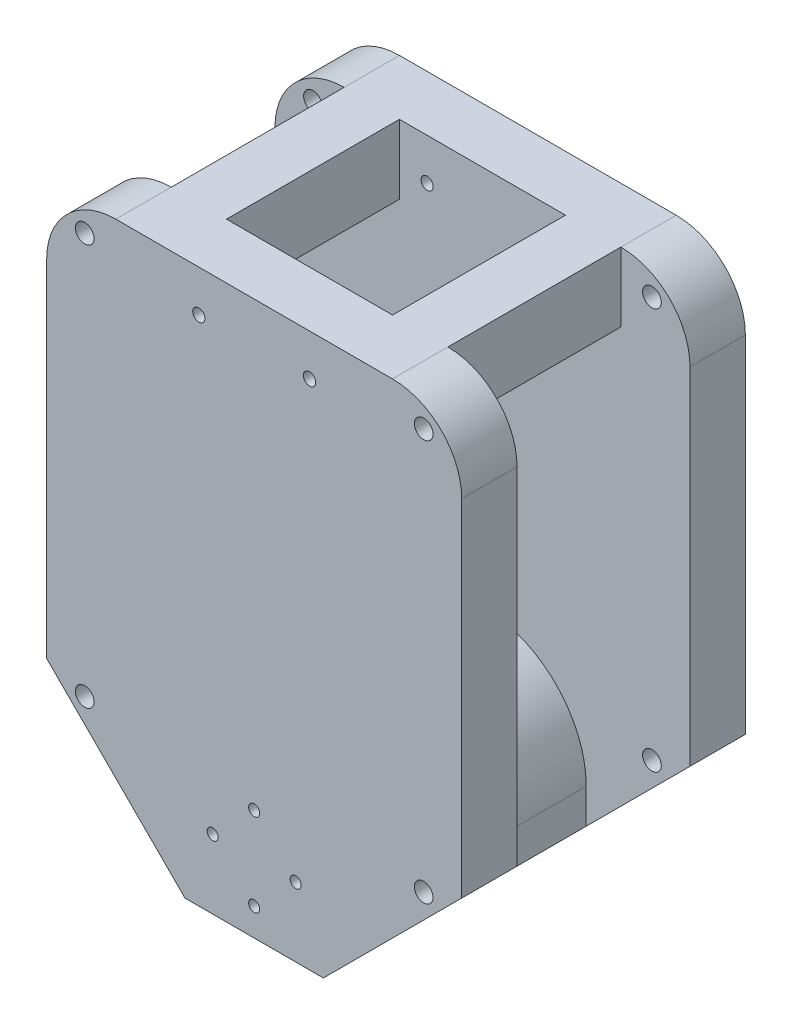
SolidWorks part; units mm, degrees
ref_plane "Front Plane" through (0, 0, 0) normal (0, 0, 1) x (1, 0, 0)
ref_plane "Top Plane" through (0, 0, 0) normal (0, 1, 0) x (1, 0, 0)
ref_plane "Right Plane" through (0, 0, 0) normal (1, 0, 0) x (0, 0, -1)
sketch "Sketch1" plane through (0, 0, 0) normal (0, 0, 1) x (1, 0, 0)
  line L11 (-30, 20.2064) -> (0, 20.2064)
  line L12 (0, 20.2064) -> (30, 20.2064)
  line L13 (30, 20.2064) -> (30, -59.7936)
  line L14 (30, -59.7936) -> (-30, -59.7936)
  line L15 (-30, -59.7936) -> (-30, 20.2064)
  circle A0 centre (-8, 14.2064) radius 0.8836
  circle A1 centre (8, 14.2064) radius 0.8966
  circle A2 centre (0, -49.7936) radius 8 construction
  circle A3 centre (0, -49.7936) radius 6 construction
  circle A4 centre (0, -43.7936) radius 0.8
  circle A5 centre (6, -49.7936) radius 0.8
  circle A6 centre (0, -55.7936) radius 0.8
  circle A7 centre (-6, -49.7936) radius 0.8
  circle A8 centre (-24.5, 16.2064) radius 1.35
  circle A9 centre (24.5, 16.2064) radius 1.35
  circle A10 centre (-24.5, -41.7936) radius 1.35
  circle A11 centre (24.5, -41.7936) radius 1.35
  point P25 (0, -49.7936)
  point P31 (0, 0)
  point P32 (0, 0)
  point P33 (0, 0)
  point P34 (0, 0)
  point P35 (0, 0)
  dimension "D7" = 4
  dimension "D10" = 49
  dimension "D1" = 8
  dimension "D2" = 30
  dimension "D3" = 30
  dimension "D4" = 16
  dimension "D5" = 0
  dimension "D6" = 80
  dimension "D8" = 10
  dimension "D9" = 6
  dimension "D11" = 24.5
  dimension "D12" = 58
  dimension "D13" = 4
extrude "Boss-Extrude1" add sketch "Sketch1" along normal blind 8
sketch "Sketch2" plane through (0, 0, 8) normal (0, 0, 1) x (1, 0, 0)
  line L0 (-12, 20.2064) -> (-12, 10.2064)
  line L1 (30, 20.2064) -> (-30, 20.2064) construction
  line L2 (12, 20.2064) -> (12, 10.2064)
  line L3 (12, 20.2064) -> (20, 20.2064)
  line L4 (20, 20.2064) -> (20, 10.2064)
  line L5 (20, 10.2064) -> (12, 10.2064)
  line L6 (-12, 20.2064) -> (-20, 20.2064)
  line L7 (-20, 20.2064) -> (-20, 10.2064)
  line L8 (-20, 10.2064) -> (-12, 10.2064)
  dimension "D1" = 12
  dimension "D2" = 12
  dimension "D3" = 10
  dimension "D4" = 8
  dimension "D5" = 8
extrude "Boss-Extrude3" add sketch "Sketch2" along normal blind 25
extrude "Boss-Extrude4" add sketch "Sketch1<2>" against normal blind 8 from offset 41
sketch "Sketch1<2>" plane through (0, 0, 0) normal (0, 0, 1) x (1, 0, 0) same geometry as "Sketch1"
sketch "Sketch3" plane through (0, 0, 8) normal (0, 0, 1) x (1, 0, 0)
  line L4 (-30, -59.7936) -> (-10, -59.7936) construction
  line L5 (-6, -49.7936) -> (6, -49.7936) construction
  line L6 (-10, -49.7936) -> (-10, -59.7936)
  line L7 (0, -43.7936) -> (0, -55.7936) construction
  line L8 (10, -49.7936) -> (10, -59.7936)
  line L9 (10, -59.7936) -> (30, -59.7936) construction
  line L10 (-10, -59.7936) -> (10, -59.7936)
  arc A1 (10, -49.7936) -> (-10, -49.7936) centre (0, -49.7936) ccw
extrude "Cut-Extrude1" cut sketch "Sketch3" against normal blind 3
extrude "Cut-Extrude2" cut sketch "Sketch3<2>" along normal blind 3 from surface starting at face at (25.85, -41.7936, 33)
sketch "Sketch3<2>" plane through (0, 0, 8) normal (0, 0, 1) x (1, 0, 0) same geometry as "Sketch3"
sketch "Sketch4" plane through (0, 0, 33) normal (0, 0, -1) x (-1, 0, 0)
  line L0 (-15, -49.7936) -> (-15, -59.7936)
  line L1 (15, -49.7936) -> (15, -59.7936)
  line L2 (-10, -49.7936) -> (-10, -59.7936)
  line L3 (15, -59.7936) -> (30, -59.7936)
  line L4 (-15, -59.7936) -> (-10, -59.7936)
  line L5 (10, -49.7936) -> (10, -59.7936)
  line L6 (-15, -59.7936) -> (-10, -59.7936)
  line L7 (10, -59.7936) -> (15, -59.7936)
  line L8 (15, -59.7936) -> (10, -59.7936)
  line L10 (-15, -59.7936) -> (-10, -59.7936)
  line L11 (10, -59.7936) -> (15, -59.7936)
  line L15 (-30, -59.7936) -> (-10, -59.7936)
  line L16 (-10, -59.7936) -> (-10, -49.7936)
  line L17 (10, -49.7936) -> (10, -59.7936)
  line L18 (10, -59.7936) -> (30, -59.7936)
  line L19 (30, -59.7936) -> (30, 20.2064)
  line L20 (30, 20.2064) -> (20, 20.2064)
  line L21 (20, 20.2064) -> (20, 10.2064)
  line L22 (20, 10.2064) -> (12, 10.2064)
  line L23 (12, 10.2064) -> (12, 20.2064)
  line L24 (12, 20.2064) -> (-12, 20.2064)
  line L25 (-12, 20.2064) -> (-12, 10.2064)
  line L26 (-12, 10.2064) -> (-20, 10.2064)
  line L27 (-20, 10.2064) -> (-20, 20.2064)
  line L28 (-20, 20.2064) -> (-30, 20.2064)
  line L29 (-30, 20.2064) -> (-30, -59.7936)
  line L30 (-30, -59.7936) -> (-15, -59.7936)
  line L34 (30, -59.7936) -> (30, 20.2064)
  line L35 (30, 20.2064) -> (20, 20.2064)
  line L36 (20, 20.2064) -> (20, 10.2064)
  line L37 (20, 10.2064) -> (12, 10.2064)
  line L38 (12, 10.2064) -> (12, 20.2064)
  line L39 (12, 20.2064) -> (-12, 20.2064)
  line L40 (-12, 20.2064) -> (-12, 10.2064)
  line L41 (-12, 10.2064) -> (-20, 10.2064)
  line L42 (-20, 10.2064) -> (-20, 20.2064)
  line L43 (-20, 20.2064) -> (-30, 20.2064)
  line L44 (-30, 20.2064) -> (-30, -59.7936)
  arc A0 (15, -49.7936) -> (-15, -49.7936) centre (0, -49.7936) ccw
  arc A1 (10, -49.7936) -> (-10, -49.7936) centre (0, -49.7936) ccw
  arc A2 (10, -49.7936) -> (-10, -49.7936) centre (0, -49.7936) ccw
  arc A3 (10, -49.7936) -> (-10, -49.7936) centre (0, -49.7936) ccw
  arc A4 (-10, -49.7936) -> (9.3304, -53.3913) centre (0, -49.7936) cw
  dimension "D1" = 0
sketch "Sketch5" plane through (0, 0, 33) normal (0, 0, -1) x (-1, 0, 0)
  line L0 (-15, -49.7936) -> (-15, -59.7936)
  line L1 (-15, -59.7936) -> (-10, -59.7936)
  line L2 (-10, -59.7936) -> (-10, -49.7936)
  line L3 (10, -49.7936) -> (10, -59.7936)
  line L4 (10, -59.7936) -> (15, -59.7936)
  line L5 (15, -59.7936) -> (15, -49.7936)
  arc A0 (10, -49.7936) -> (-10, -49.7936) centre (0, -49.7936) ccw
  arc A1 (15, -49.7936) -> (-15, -49.7936) centre (0, -49.7936) ccw
extrude "Boss-Extrude5" add sketch "Sketch5" along normal blind 25
sketch "Sketch7" plane through (0, 0, 41) normal (0, 0, 1) x (1, 0, 0)
  line L1 (30, 20.2064) -> (30, -59.7936) construction
  line L2 (30, -39.7936) -> (30, -59.7936)
  line L6 (-30, -59.7936) -> (-30, 20.2064) construction
  line L7 (-30, -39.7936) -> (-30, -59.7936)
  line L8 (-30, -39.7936) -> (-10, -59.7936)
  line L9 (10, -59.7936) -> (30, -39.7936)
  line L10 (-30, -59.7936) -> (-10, -59.7936)
  line L11 (10, -59.7936) -> (30, -59.7936)
  dimension "D1" = 20
extrude "Cut-Extrude3" cut sketch "Sketch7" against normal blind 41
fillet "Fillet5" radius 10 4 edges at (-30, 20.2064, 37) (-30, 20.2064, 4) (30, 20.2064, 4) (30, 20.2064, 37)
